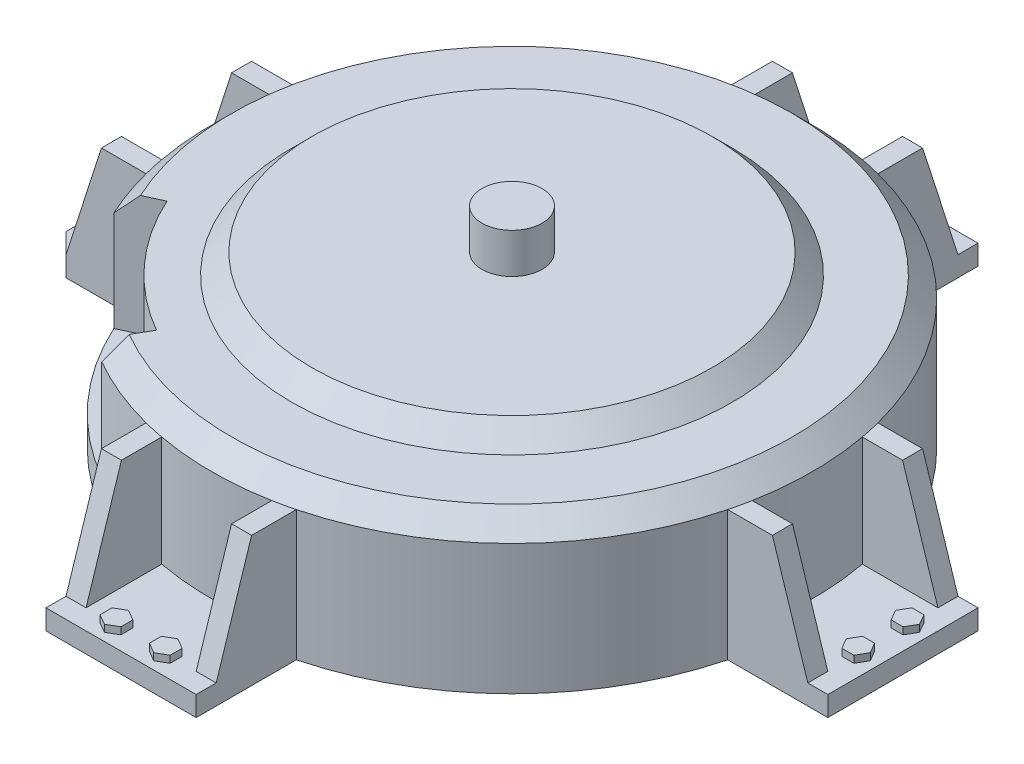
SolidWorks part; units mm, degrees
ref_plane "Front Plane" through (0, 0, 0) normal (0, 0, 1) x (1, 0, 0)
ref_plane "Top Plane" through (0, 0, 0) normal (0, 1, 0) x (1, 0, 0)
ref_plane "Right Plane" through (0, 0, 0) normal (1, 0, 0) x (0, 0, -1)
sketch "Sketch1" plane through (0, 0, 0) normal (0, 1, 0) x (1, 0, 0)
  circle A0 centre (0, 0) radius 150
  dimension "D1" = 300
extrude "Boss-Extrude1" add sketch "Sketch1" along normal blind 75
chamfer "Chamfer1" distance 10 angle 45 1 edges at (0, 75, 150)
sketch "Sketch2" plane through (0, 0, 0) normal (0, -1, 0) x (1, 0, 0)
  line L2 (-145.2369, -37.5) -> (-195.2369, -37.5)
  line L4 (-145.2369, 37.5) -> (-195.2369, 37.5)
  line L5 (-195.2369, -37.5) -> (-195.2369, 37.5)
  line L6 (-150, 0) -> (-195.2369, 37.5) construction
  line L7 (-150, 0) -> (-195.2369, -37.5) construction
  circle A0 centre (0, 0) radius 150 construction
  circle A1 centre (0, 0) radius 150
  circle M6 centre (0, 0) radius 150
  dimension "D1" = 75
  dimension "D2" = 50
extrude "Boss-Extrude2" add sketch "Sketch2" against normal blind 10 contours L5 L2 L4 M6 region at (-171.8083, 0, 0)
chamfer "Chamfer2" distance 10 angle 45 2 edges at (-195.2369, 5, -37.5) (-195.2369, 5, 37.5)
sketch "Sketch4" plane through (0, 0, 37.5) normal (0, 0, 1) x (1, 0, 0)
  line L0 (-145.2369, 10) -> (-145.2369, 65)
  line L1 (-150, 65) -> (150, 65) construction
  line L2 (-145.2369, 65) -> (-167.5569, 65)
  line L3 (-167.5569, 65) -> (-185.2369, 10)
  line L4 (-145.2369, 10) -> (-185.2369, 10) construction
  line L5 (-145.2369, 10) -> (-185.2369, 10)
  line L8 (-145.2369, 10) -> (-185.2369, 10)
  line L9 (-185.2369, 10) -> (-185.2369, 0)
  line L10 (-185.2369, 0) -> (-145.2369, 0)
  line L11 (-145.2369, 0) -> (-145.2369, 10)
  line L13 (-185.2369, 10) -> (-185.2369, 0)
  line L14 (-185.2369, 0) -> (-145.2369, 0)
  line L15 (-145.2369, 0) -> (-145.2369, 10)
  line M2 (-145.2369, 10) -> (-185.2369, 10)
  dimension "D1" = 17.68
  dimension "D2" = 0
extrude "Boss-Extrude3" add sketch "Sketch4" against normal blind 10 contours L2 L3 L0 M2 region at (-161.2349, 34.8994, 37.5)
sketch "Sketch5" plane through (0, 10, 0) normal (0, 1, 0) x (1, 0, 0)
  line L0 (-185.2369, -37.5) -> (-185.2369, 37.5) construction
  line L3 (-182.2677, -17.5178) -> (-179.237, -12.3396)
  line L4 (-179.237, -12.3396) -> (-182.2061, -7.1257)
  line L5 (-182.2061, -7.1257) -> (-188.206, -7.0901)
  line L6 (-188.206, -7.0901) -> (-191.2368, -12.2684)
  line L7 (-191.2368, -12.2684) -> (-188.2676, -17.4823)
  line L8 (-188.2676, -17.4823) -> (-182.2677, -17.5178)
  line L11 (-185.2677, -17.5) -> (-185.2369, -27.5) construction
  circle A0 centre (-185.2369, -12.304) radius 5.1962 construction
  dimension "D1" = 6
  dimension "D2" = 10
extrude "Boss-Extrude4" add sketch "Sketch5" along normal blind 3.5
mirror "Mirror2" about plane through (0, 0, 0) normal (0, 0, 1) of "Boss-Extrude3", "Boss-Extrude4"
pattern_circular "CirPattern2" count 4 over 360 about axis through (0, 75, 0) along (0, 1, 0) of "Boss-Extrude4", "Mirror2", "Boss-Extrude2", "Boss-Extrude3"
sketch "Sketch6" plane through (0, 75, 0) normal (0, 1, 0) x (1, 0, 0)
  line L2 (-118.1912, -54.1371) -> (-136.3745, -62.4659)
  line L3 (-65, -112.5833) -> (-75, -129.9038)
  circle A0 centre (0, 0) radius 130
  arc A1 (-145.2369, -37.5) -> (-37.5, -145.2369) centre (0, 0) ccw construction
  arc A2 (-136.3745, -62.4659) -> (-75, -129.9038) centre (0, 0) ccw
  circle M6 centre (0, 0) radius 140
  dimension "D3" = 260
extrude "Cut-Extrude1" cut sketch "Sketch6" against normal blind 60 contours A0 L2 L3 M6 | L2 A2 L3 M6 region at (-98.3076, 75, 89.4687) region at (-105.5832, 75, 96.0902)
sketch "Sketch7" plane through (0, 75, 0) normal (0, 1, 0) x (1, 0, 0)
  circle A0 centre (0, 0) radius 110
  dimension "D1" = 220
extrude "Boss-Extrude5" add sketch "Sketch7" along normal blind 10
chamfer "Chamfer3" distance 10 angle 45 1 edges at (0, 85, 110)
sketch "Sketch8" plane through (0, 85, 0) normal (0, 1, 0) x (1, 0, 0)
  circle A0 centre (0, 0) radius 15
  dimension "D1" = 30
extrude "Boss-Extrude7" add sketch "Sketch8" along normal blind 20
